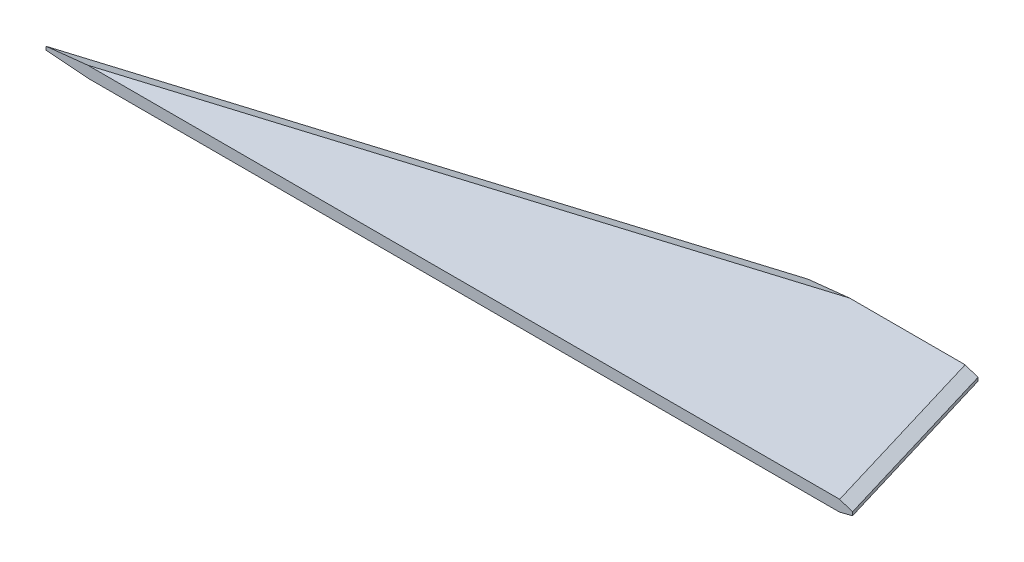
SolidWorks part; units mm, degrees
material "Thornel Mat VMA"
ref_plane "Front Plane" through (0, 0, 0) normal (0, 0, 1) x (1, 0, 0)
ref_plane "Top Plane" through (0, 0, 0) normal (0, 1, 0) x (1, 0, 0)
ref_plane "Right Plane" through (0, 0, 0) normal (1, 0, 0) x (0, 0, -1)
sketch "Sketch1" plane through (0, 0, 0) normal (0, 1, 0) x (1, 0, 0)
  line L0 (0, 0) -> (228.6, 0)
  line L1 (165.1, 50.8) -> (213.36, 50.8)
  line L2 (0, 0) -> (165.1, 50.8)
  line L3 (213.36, 50.8) -> (228.6, 0)
  dimension "D1" = 48.26
  dimension "D2" = 228.6
  dimension "D3" = 165.1
  dimension "D4" = 50.8
extrude "Boss-Extrude1" add sketch "Sketch1" along normal blind 3.175
chamfer "Chamfer1" distance 1.27 angle 70 2 edges at (82.55, 3.175, -25.4) (220.98, 3.175, -25.4) first distance on face at (82.55, 1.5875, -25.4) first distance on face at (220.98, 1.5875, -25.4)
chamfer "Chamfer2" distance 3.556 angle 15 2 edges at (220.98, 0, -25.4) (82.55, 0, -25.4) first distance on face at (151.765, 0, -25.4)
